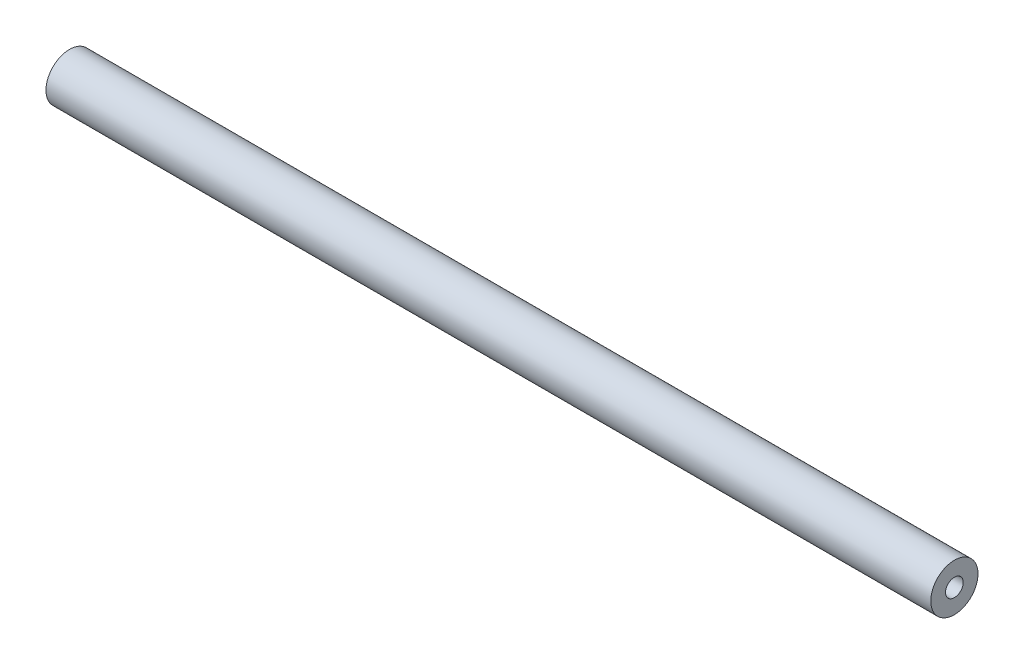
SolidWorks part; units mm, degrees
ref_plane "Front" through (0, 0, 0) normal (0, 0, 1) x (1, 0, 0)
ref_plane "Top" through (0, 0, 0) normal (0, 1, 0) x (1, 0, 0)
ref_plane "Right" through (0, 0, 0) normal (1, 0, 0) x (0, 0, -1)
sketch "Sketch1" plane through (0, 0, 0) normal (0, 0, 1) x (1, 0, 0)
  line L0 (0, 4) -> (0, 1.5)
  line L1 (0, 1.5) -> (149.86, 1.5)
  line L2 (149.86, 1.5) -> (149.86, 4)
  line L3 (149.86, 4) -> (0, 4)
  line L4 (0, 0) -> (149.86, 0) construction
revolve "Revolve1" add sketch "Sketch1" angle 360 about L4 reverse direction yes
